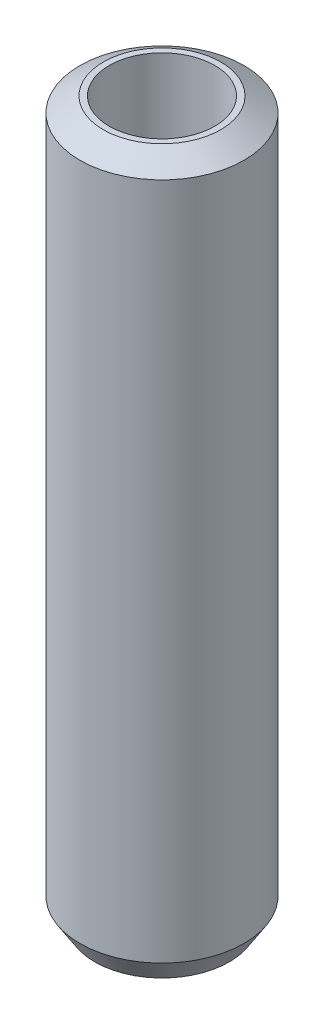
SolidWorks part; units mm, degrees
ref_plane "Front Plane" through (0, 0, 0) normal (0, 0, 1) x (1, 0, 0)
ref_plane "Top Plane" through (0, 0, 0) normal (0, 1, 0) x (1, 0, 0)
ref_plane "Right Plane" through (0, 0, 0) normal (1, 0, 0) x (0, 0, -1)
sketch "Sketch1" plane through (0, 0, 0) normal (0, 1, 0) x (1, 0, 0)
  circle A0 centre (0, 0) radius 30
  dimension "SHAFT_OD" = 60
extrude "Boss-Extrude1" add sketch "Sketch1" along normal blind 261.8673
sketch "Sketch2" plane through (0, 0, 0) normal (0, 1, 0) x (1, 0, 0)
  circle A0 centre (0, 0) radius 19.2737
  dimension "BORE_D" = 38.5474
extrude "Cut-Extrude1" cut sketch "Sketch2" along normal through all
chamfer "Chamfer1" distance 5.3967 angle 57.708 2 edges at (0, 261.8673, 30) (0, 0, 30) first distance on face at (0, 261.8673, 30) first distance on face at (0, 0, 19.2737)
